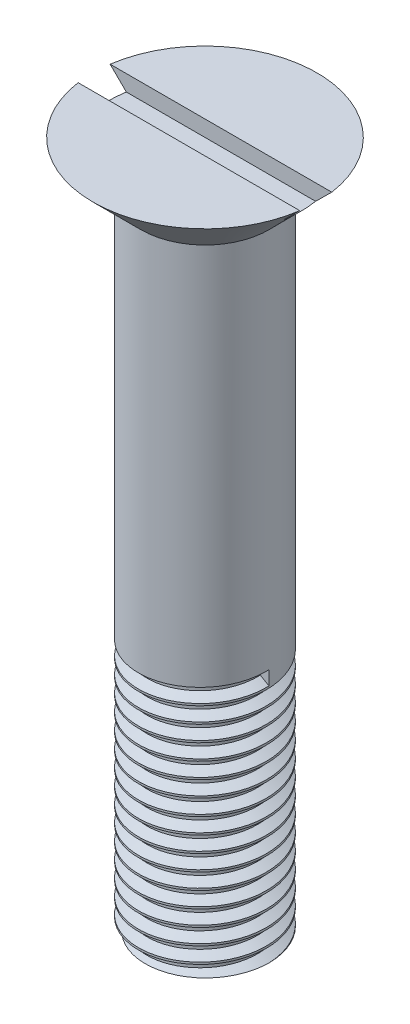
SolidWorks part; units mm, degrees
material "Gray Cast Iron"
ref_plane "Front Plane" through (0, 0, 0) normal (0, 0, 1) x (1, 0, 0)
ref_plane "Top Plane" through (0, 0, 0) normal (0, 1, 0) x (1, 0, 0)
ref_plane "Right Plane" through (0, 0, 0) normal (1, 0, 0) x (0, 0, -1)
sketch "Sketch1" plane through (0, 0, 0) normal (0, 0, 1) x (1, 0, 0)
  line L0 (0, 0) -> (0, -99373.5245) construction
  line L1 (0, 0) -> (99373.5245, 0) construction
  line L2 (0, 0) -> (0, 45)
  line L3 (0, 45) -> (7, 45)
  line L4 (7, 45) -> (4, 42)
  line L5 (4, 42) -> (4, 2.3094)
  line L6 (4, 2.3094) -> (0, 0)
  dimension "D1" = 45
  dimension "D2" = 3
  dimension "D3" = 45
  dimension "D4" = 8
  dimension "D5" = 60
revolve "Revolve1" add sketch "Sketch1" angle 360 about L0
sketch "Sketch2" plane through (0, 45, 0) normal (0, 1, 0) x (1, 0, 0)
  line L1 (-7, 1) -> (7, 1)
  line L2 (-7, 1) -> (-7, -1)
  line L3 (-7, -1) -> (7, -1)
  line L4 (7, 1) -> (7, -1)
  line L5 (-7, 1) -> (7, -1) construction
  line L6 (-7, -1) -> (7, 1) construction
  circle A0 centre (0, 0) radius 7 construction
  point P0 (0, 0)
  dimension "D1" = 2
extrude "Cut-Extrude1" cut sketch "Sketch2" against normal blind 1
thread "Thread1" pitch 1 method cut profile "Thread Profile1" start angle 0, offset 2, length 17, pitch 1, diameter 8
ref_plane "Plane1" through (4, 0.3094, 0) normal (0, 0, 1) x (1, 0, 0)
sketch "Thread Profile1" plane through (4, 0.3094, 0) normal (0, 0, 1) x (1, 0, 0)
  line L0 (0, 0) -> (0, 1) construction
  line L11 (0, 0) -> (0, 0.875)
  line L12 (0, 0.875) -> (-0.5413, 0.5625)
  line L13 (-0.5413, 0.5625) -> (-0.5413, 0.3125)
  line L15 (-0.5413, 0.3125) -> (0, 0)
  line L17 (-0.5413, 0.4375) -> (0, 0.4375) construction
  point P2 (0, 0)
  dimension "Pitch" = 1
  dimension "Profile_Angle" = 60
  dimension "Profile_Land" = 0.25
  dimension "Profile_Height" = 0.5413
